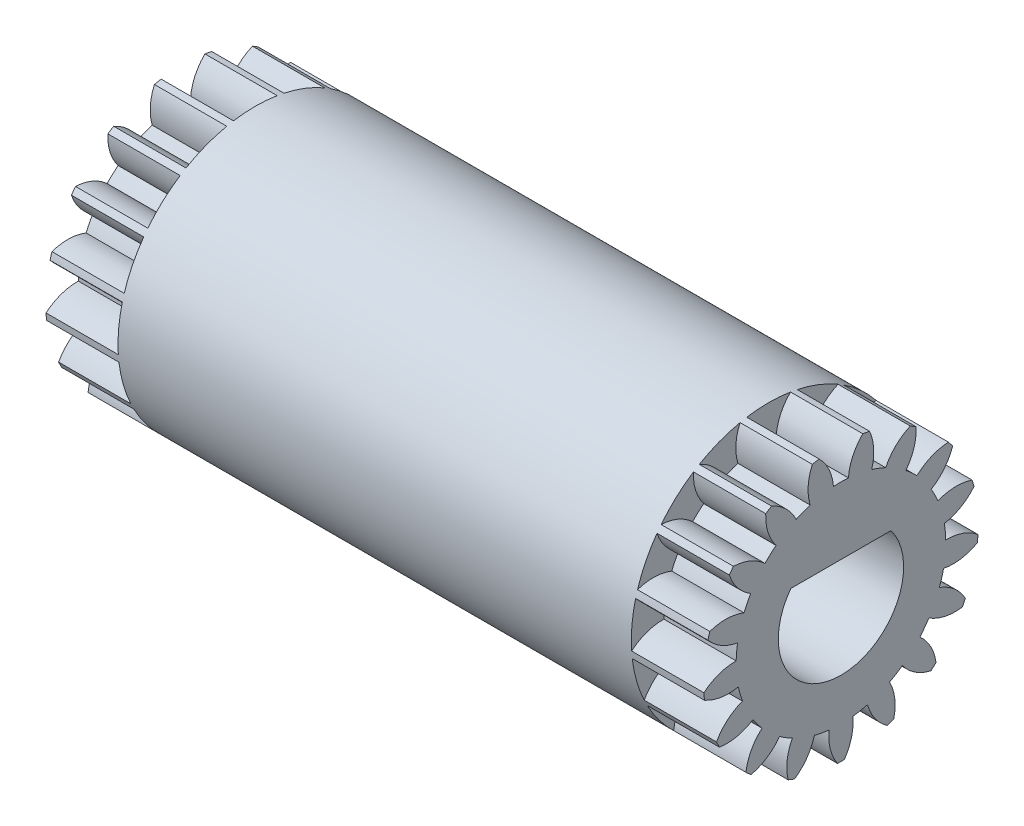
SolidWorks part; units mm, degrees
ref_plane "Plane1" through (0, 0, 0) normal (0, 0, 1) x (1, 0, 0)
ref_plane "Plane2" through (0, 0, 0) normal (0, 1, 0) x (1, 0, 0)
ref_plane "Plane3" through (0, 0, 0) normal (1, 0, 0) x (0, 0, -1)
other "Configuration Table"
sketch "HoldingSke" plane through (0, 0, 0) normal (0, 1, 0) x (1, 0, 0)
  line L0 (0, 0) -> (1.5938, -0.4873)
  line L1 (-15, 0) -> (100, 0) construction
  line L2 (0, 0) -> (-2.1039, 2.3779)
  line L3 (0, 0) -> (-11.863, 4.5341)
  line L4 (0, 0) -> (8.2586, 2.5249)
  line L5 (0, 0) -> (-46.8476, -17.4728)
  line L6 (0, 0) -> (-2.4869, -1.6779)
  line L7 (-2.1039, 2.3779) -> (8.6586, 51.2059)
  line L8 (-76.2, 54.61) -> (-75.3, 54.61)
  line L9 (-71.009, 38.7566) -> (-53.1078, 45.2721)
  line L10 (-76.2, 71.12) -> (104.1128, 71.12)
  line L11 (0, 0) -> (-3, 0)
  line L12 (-76.2, 101.6) -> (-76.177, 101.6)
  line L13 (24.9733, 27.94) -> (52.9518, 28.4284)
  line L14 (24.9733, 27.94) -> (24.9743, 27.94)
  line L15 (24.9733, 27.94) -> (100.4006, 29.5858)
  line L16 (-63.627, -0.6) -> (-12.827, -0.6)
  circle A0 centre (0, 0) radius 2.5
  circle A1 centre (0, 0) radius 1.5
  circle A2 centre (0, 0) radius 1.5
  circle A3 centre (0, 0) radius 2.5
  dimension "Num_teeth" = 17
  dimension "Pitch_radius" = 180.3128
  dimension "Width" = 3
  dimension "Thickness" = 3
sketch "BasProSke" plane through (0, 0, 0) normal (0, 1, 0) x (1, 0, 0)
  line L0 (-10, 0) -> (60, 0) construction
  line L1 (0, 0) -> (0, 5.7)
  line L2 (0, 0) -> (3, 0)
  line L3 (3, 0) -> (3, 5.7)
  line L4 (3, 5.7) -> (0, 5.7)
  dimension "Thickness" = 3
  dimension "Diameter" = 11.4
revolve "Base-Revolve" add sketch "BasProSke" angle 360 about L0
sketch "TooCutSke" plane through (0, 0, 0) normal (1, 0, 0) x (0, 0, -1)
  line L1 (0, 0) -> (0, 107) construction
  line L2 (0, 0) -> (-0.5108, 5.0744) construction
  line L3 (0, 0) -> (-1.8676, 9.9906) construction
  line L4 (-0.5108, 5.0744) -> (-0.9338, 4.9953) construction
  arc A0 (0.3104, 4.3379) -> (-0.3104, 4.3379) centre (0, 0) ccw
  arc A1 (0.9293, 5.6495) -> (-0.9293, 5.6495) centre (0, 0) ccw
  circle A2 centre (0, 0) radius 5.1 construction
  circle A3 centre (0, 0) radius 4.7924 construction
  arc A4 (-0.3104, 4.3379) -> (-0.9293, 5.6495) centre (-2.3443, 4.1799) ccw
  arc A5 (0.9293, 5.6495) -> (0.3104, 4.3379) centre (2.3443, 4.1799) ccw
extrude "ToothCut" cut sketch "TooCutSke" along normal through all
fillet "Breaks" [suppressed] radius 0.012 tangent propagation no
fillet "RootFillets" [suppressed] radius 0.151
pattern_circular "TeethCuts" count 17 every 21.176 about axis through (-10, 0, 0) along (1, 0, 0) of "ToothCut", "RootFillets", "Breaks"
sketch "HubNeaOneSke" plane through (0, 0, 0) normal (-1, 0, 0) x (0, 0, 1)
  circle A0 centre (0, 0) radius 1.5
  dimension "Diameter" = 3
extrude "HubNearOne" [suppressed] add sketch "HubNeaOneSke" along normal blind 47.0001
sketch "HubNeaBotSke" plane through (0, 0, 0) normal (-1, 0, 0) x (0, 0, 1)
  circle A0 centre (0, 0) radius 1.5
  dimension "Diameter" = 3
extrude "HubNearBoth" add sketch "HubNeaBotSke" along normal blind 23.5
ref_plane "FarPln" through (3, 0, 0) normal (1, 0, 0) x (0, 0, -1)
sketch "HubFarSke" plane through (3, 0, 0) normal (1, 0, 0) x (0, 0, -1)
  circle A0 centre (0, 0) radius 1.5
  dimension "Diameter" = 3
extrude "HubFar" add sketch "HubFarSke" along normal blind 23.5
sketch "BorSke" plane through (0, 0, 0) normal (1, 0, 0) x (0, 0, -1)
  circle A0 centre (0, 0) radius 2.5
  dimension "Diameter" = 5
extrude "Bore" cut sketch "BorSke" along normal mid plane 100.0001
sketch "KeySke" plane through (0, 0, 0) normal (1, 0, 0) x (0, 0, -1)
  line L0 (-1, 0) -> (-1, 3.4)
  line L1 (-1, 3.4) -> (1, 3.4)
  line L2 (1, 3.4) -> (1, 0)
  line L3 (0, 0) -> (0, 34) construction
  line L4 (-1, 0) -> (1, 0)
  dimension "Width" = 2
extrude "Keyway" [suppressed] cut sketch "KeySke" along normal mid plane 100.0001
pattern_circular "Keyway2" [suppressed] count 2 every 90 about axis through (-10, 0, 0) along (1, 0, 0) reverse direction yes
sketch "草图2" plane through (3, 0, 0) normal (1, 0, 0) x (0, 0, -1)
  circle A0 centre (0, 0) radius 5.7
extrude "凸台-拉伸1" add sketch "草图2" along normal blind 21.3
sketch "草图3" plane through (24.3, 0, 0) normal (1, 0, 0) x (0, 0, -1)
  arc A68 (-5.5197, 1.4221) -> (-4.2908, 0.7093) centre (-3.9458, 2.7199) ccw
  arc A69 (-5.4416, 1.6967) -> (-5.5197, 1.4221) centre (0, 0) ccw
  arc A70 (-4.0215, 1.6557) -> (-5.4416, 1.6967) centre (-4.7867, -0.2353) ccw
  arc A71 (-3.7448, 2.2114) -> (-4.0215, 1.6557) centre (0, 0) ccw
  arc A72 (-4.6333, 3.3201) -> (-3.7448, 2.2114) centre (-2.6968, 3.9617) ccw
  arc A73 (-4.4613, 3.5478) -> (-4.6333, 3.3201) centre (0, 0) ccw
  arc A74 (-3.1518, 2.9966) -> (-4.4613, 3.5478) centre (-4.5484, 1.5097) ccw
  arc A75 (-2.6931, 3.4149) -> (-3.1518, 2.9966) centre (0, 0) ccw
  arc A76 (-3.1211, 4.7696) -> (-2.6931, 3.4149) centre (-1.0836, 4.6683) ccw
  arc A77 (-2.8784, 4.9198) -> (-3.1211, 4.7696) centre (0, 0) ccw
  arc A78 (-1.8565, 3.9329) -> (-2.8784, 4.9198) centre (-3.6959, 3.0508) ccw
  arc A79 (-1.2776, 4.1571) -> (-1.8565, 3.9329) centre (0, 0) ccw
  arc A80 (-1.1873, 5.575) -> (-1.2776, 4.1571) centre (0.676, 4.7445) ccw
  arc A81 (-0.9068, 5.6274) -> (-1.1873, 5.575) centre (0, 0) ccw
  arc A82 (-0.3104, 4.3379) -> (-0.9068, 5.6274) centre (-2.3443, 4.1799) ccw
  arc A83 (0.3104, 4.3379) -> (-0.3104, 4.3379) centre (0, 0) ccw
  arc A84 (0.9068, 5.6274) -> (0.3104, 4.3379) centre (2.3443, 4.1799) ccw
  arc A85 (1.1873, 5.575) -> (0.9068, 5.6274) centre (0, 0) ccw
  arc A86 (1.2776, 4.1571) -> (1.1873, 5.575) centre (-0.676, 4.7445) ccw
  arc A87 (1.8565, 3.9329) -> (1.2776, 4.1571) centre (0, 0) ccw
  arc A88 (2.8784, 4.9198) -> (1.8565, 3.9329) centre (3.6959, 3.0508) ccw
  arc A89 (3.1211, 4.7696) -> (2.8784, 4.9198) centre (0, 0) ccw
  arc A90 (2.6931, 3.4149) -> (3.1211, 4.7696) centre (1.0836, 4.6683) ccw
  arc A91 (3.1518, 2.9966) -> (2.6931, 3.4149) centre (0, 0) ccw
  arc A92 (4.4613, 3.5478) -> (3.1518, 2.9966) centre (4.5484, 1.5097) ccw
  arc A93 (4.6333, 3.3201) -> (4.4613, 3.5478) centre (0, 0) ccw
  arc A94 (3.7448, 2.2114) -> (4.6333, 3.3201) centre (2.6968, 3.9617) ccw
  arc A95 (4.0215, 1.6557) -> (3.7448, 2.2114) centre (0, 0) ccw
  arc A96 (5.4416, 1.6967) -> (4.0215, 1.6557) centre (4.7867, -0.2353) ccw
  arc A97 (5.5197, 1.4221) -> (5.4416, 1.6967) centre (0, 0) ccw
  arc A98 (4.2908, 0.7093) -> (5.5197, 1.4221) centre (3.9458, 2.7199) ccw
  arc A99 (4.348, 0.0912) -> (4.2908, 0.7093) centre (0, 0) ccw
  arc A100 (5.6871, -0.3837) -> (4.348, 0.0912) centre (4.3784, -1.9486) ccw
  arc A101 (5.6607, -0.6679) -> (5.6871, -0.3837) centre (0, 0) ccw
  arc A102 (4.2573, -0.8886) -> (5.6607, -0.6679) centre (4.6619, 1.1109) ccw
  arc A103 (4.0874, -1.4857) -> (4.2573, -0.8886) centre (0, 0) ccw
  arc A104 (5.1644, -2.4122) -> (4.0874, -1.4857) centre (3.3788, -3.3987) ccw
  arc A105 (5.0372, -2.6677) -> (5.1644, -2.4122) centre (0, 0) ccw
  arc A106 (3.6488, -2.3665) -> (5.0372, -2.6677) centre (4.7484, -0.6482) ccw
  arc A107 (3.2747, -2.8619) -> (3.6488, -2.3665) centre (0, 0) ccw
  arc A108 (3.9443, -4.1149) -> (3.2747, -2.8619) centre (1.9229, -4.3897) ccw
  arc A109 (3.7334, -4.3072) -> (3.9443, -4.1149) centre (0, 0) ccw
  arc A110 (2.5475, -3.5248) -> (3.7334, -4.3072) centre (4.1936, -2.3198) ccw
  arc A111 (2.0197, -3.8516) -> (2.5475, -3.5248) centre (0, 0) ccw
  arc A112 (2.1915, -5.2619) -> (2.0197, -3.8516) centre (0.2073, -4.7879) ccw
  arc A113 (1.9254, -5.365) -> (2.1915, -5.2619) centre (0, 0) ccw
  arc A114 (1.1022, -4.207) -> (1.9254, -5.365) centre (3.0724, -3.678) ccw
  arc A115 (0.492, -4.3211) -> (1.1022, -4.207) centre (0, 0) ccw
  arc A116 (0.1427, -5.6982) -> (0.492, -4.3211) centre (-1.5363, -4.5395) ccw
  arc A117 (-0.1427, -5.6982) -> (0.1427, -5.6982) centre (0, 0) ccw
  arc A118 (-0.492, -4.3211) -> (-0.1427, -5.6982) centre (1.5363, -4.5395) ccw
  arc A119 (-1.1022, -4.207) -> (-0.492, -4.3211) centre (0, 0) ccw
  arc A120 (-1.9254, -5.365) -> (-1.1022, -4.207) centre (-3.0724, -3.678) ccw
  arc A121 (-2.1915, -5.2619) -> (-1.9254, -5.365) centre (0, 0) ccw
  arc A122 (-2.0197, -3.8516) -> (-2.1915, -5.2619) centre (-0.2073, -4.7879) ccw
  arc A123 (-2.5475, -3.5248) -> (-2.0197, -3.8516) centre (0, 0) ccw
  arc A124 (-3.7334, -4.3072) -> (-2.5475, -3.5248) centre (-4.1936, -2.3198) ccw
  arc A125 (-3.9443, -4.1149) -> (-3.7334, -4.3072) centre (0, 0) ccw
  arc A126 (-3.2747, -2.8619) -> (-3.9443, -4.1149) centre (-1.9229, -4.3897) ccw
  arc A127 (-3.6488, -2.3665) -> (-3.2747, -2.8619) centre (0, 0) ccw
  arc A128 (-5.0372, -2.6677) -> (-3.6488, -2.3665) centre (-4.7484, -0.6482) ccw
  arc A129 (-5.1644, -2.4122) -> (-5.0372, -2.6677) centre (0, 0) ccw
  arc A130 (-4.0874, -1.4857) -> (-5.1644, -2.4122) centre (-3.3788, -3.3987) ccw
  arc A131 (-4.2573, -0.8886) -> (-4.0874, -1.4857) centre (0, 0) ccw
  arc A132 (-5.6607, -0.6679) -> (-4.2573, -0.8886) centre (-4.6619, 1.1109) ccw
  arc A133 (-5.6871, -0.3837) -> (-5.6607, -0.6679) centre (0, 0) ccw
  arc A134 (-4.348, 0.0912) -> (-5.6871, -0.3837) centre (-4.3784, -1.9486) ccw
  arc A135 (-4.2908, 0.7093) -> (-4.348, 0.0912) centre (0, 0) ccw
  arc A136 (-5.5197, 1.4221) -> (-4.2908, 0.7093) centre (-3.9458, 2.7199) ccw
  arc A137 (-5.4416, 1.6967) -> (-5.5197, 1.4221) centre (0, 0) ccw
  arc A138 (-4.0215, 1.6557) -> (-5.4416, 1.6967) centre (-4.7867, -0.2353) ccw
  arc A139 (-3.7448, 2.2114) -> (-4.0215, 1.6557) centre (0, 0) ccw
  arc A140 (-4.6333, 3.3201) -> (-3.7448, 2.2114) centre (-2.6968, 3.9617) ccw
  arc A141 (-4.4613, 3.5478) -> (-4.6333, 3.3201) centre (0, 0) ccw
  arc A142 (-3.1518, 2.9966) -> (-4.4613, 3.5478) centre (-4.5484, 1.5097) ccw
  arc A143 (-2.6931, 3.4149) -> (-3.1518, 2.9966) centre (0, 0) ccw
  arc A144 (-3.1211, 4.7696) -> (-2.6931, 3.4149) centre (-1.0836, 4.6683) ccw
  arc A145 (-2.8784, 4.9198) -> (-3.1211, 4.7696) centre (0, 0) ccw
  arc A146 (-1.8565, 3.9329) -> (-2.8784, 4.9198) centre (-3.6959, 3.0508) ccw
  arc A147 (-1.2776, 4.1571) -> (-1.8565, 3.9329) centre (0, 0) ccw
  arc A148 (-1.1873, 5.575) -> (-1.2776, 4.1571) centre (0.676, 4.7445) ccw
  arc A149 (-0.9068, 5.6274) -> (-1.1873, 5.575) centre (0, 0) ccw
  arc A150 (-0.3104, 4.3379) -> (-0.9068, 5.6274) centre (-2.3443, 4.1799) ccw
  arc A151 (0.3104, 4.3379) -> (-0.3104, 4.3379) centre (0, 0) ccw
  arc A152 (0.9068, 5.6274) -> (0.3104, 4.3379) centre (2.3443, 4.1799) ccw
  arc A153 (1.1873, 5.575) -> (0.9068, 5.6274) centre (0, 0) ccw
  arc A154 (1.2776, 4.1571) -> (1.1873, 5.575) centre (-0.676, 4.7445) ccw
  arc A155 (1.8565, 3.9329) -> (1.2776, 4.1571) centre (0, 0) ccw
  arc A156 (2.8784, 4.9198) -> (1.8565, 3.9329) centre (3.6959, 3.0508) ccw
  arc A157 (3.1211, 4.7696) -> (2.8784, 4.9198) centre (0, 0) ccw
  arc A158 (2.6931, 3.4149) -> (3.1211, 4.7696) centre (1.0836, 4.6683) ccw
  arc A159 (3.1518, 2.9966) -> (2.6931, 3.4149) centre (0, 0) ccw
  arc A160 (4.4613, 3.5478) -> (3.1518, 2.9966) centre (4.5484, 1.5097) ccw
  arc A161 (4.6333, 3.3201) -> (4.4613, 3.5478) centre (0, 0) ccw
  arc A162 (3.7448, 2.2114) -> (4.6333, 3.3201) centre (2.6968, 3.9617) ccw
  arc A163 (4.0215, 1.6557) -> (3.7448, 2.2114) centre (0, 0) ccw
  arc A164 (5.4416, 1.6967) -> (4.0215, 1.6557) centre (4.7867, -0.2353) ccw
  arc A165 (5.5197, 1.4221) -> (5.4416, 1.6967) centre (0, 0) ccw
  arc A166 (4.2908, 0.7093) -> (5.5197, 1.4221) centre (3.9458, 2.7199) ccw
  arc A167 (4.348, 0.0912) -> (4.2908, 0.7093) centre (0, 0) ccw
  arc A168 (5.6871, -0.3837) -> (4.348, 0.0912) centre (4.3784, -1.9486) ccw
  arc A169 (5.6607, -0.6679) -> (5.6871, -0.3837) centre (0, 0) ccw
  arc A170 (4.2573, -0.8886) -> (5.6607, -0.6679) centre (4.6619, 1.1109) ccw
  arc A171 (4.0874, -1.4857) -> (4.2573, -0.8886) centre (0, 0) ccw
  arc A172 (5.1644, -2.4122) -> (4.0874, -1.4857) centre (3.3788, -3.3987) ccw
  arc A173 (5.0372, -2.6677) -> (5.1644, -2.4122) centre (0, 0) ccw
  arc A174 (3.6488, -2.3665) -> (5.0372, -2.6677) centre (4.7484, -0.6482) ccw
  arc A175 (3.2747, -2.8619) -> (3.6488, -2.3665) centre (0, 0) ccw
  arc A176 (3.9443, -4.1149) -> (3.2747, -2.8619) centre (1.9229, -4.3897) ccw
  arc A177 (3.7334, -4.3072) -> (3.9443, -4.1149) centre (0, 0) ccw
  arc A178 (2.5475, -3.5248) -> (3.7334, -4.3072) centre (4.1936, -2.3198) ccw
  arc A179 (2.0197, -3.8516) -> (2.5475, -3.5248) centre (0, 0) ccw
  arc A180 (2.1915, -5.2619) -> (2.0197, -3.8516) centre (0.2073, -4.7879) ccw
  arc A181 (1.9254, -5.365) -> (2.1915, -5.2619) centre (0, 0) ccw
  arc A182 (1.1022, -4.207) -> (1.9254, -5.365) centre (3.0724, -3.678) ccw
  arc A183 (0.492, -4.3211) -> (1.1022, -4.207) centre (0, 0) ccw
  arc A184 (0.1427, -5.6982) -> (0.492, -4.3211) centre (-1.5363, -4.5395) ccw
  arc A185 (-0.1427, -5.6982) -> (0.1427, -5.6982) centre (0, 0) ccw
  arc A186 (-0.492, -4.3211) -> (-0.1427, -5.6982) centre (1.5363, -4.5395) ccw
  arc A187 (-1.1022, -4.207) -> (-0.492, -4.3211) centre (0, 0) ccw
  arc A188 (-1.9254, -5.365) -> (-1.1022, -4.207) centre (-3.0724, -3.678) ccw
  arc A189 (-2.1915, -5.2619) -> (-1.9254, -5.365) centre (0, 0) ccw
  arc A190 (-2.0197, -3.8516) -> (-2.1915, -5.2619) centre (-0.2073, -4.7879) ccw
  arc A191 (-2.5475, -3.5248) -> (-2.0197, -3.8516) centre (0, 0) ccw
  arc A192 (-3.7334, -4.3072) -> (-2.5475, -3.5248) centre (-4.1936, -2.3198) ccw
  arc A193 (-3.9443, -4.1149) -> (-3.7334, -4.3072) centre (0, 0) ccw
  arc A194 (-3.2747, -2.8619) -> (-3.9443, -4.1149) centre (-1.9229, -4.3897) ccw
  arc A195 (-3.6488, -2.3665) -> (-3.2747, -2.8619) centre (0, 0) ccw
  arc A196 (-5.0372, -2.6677) -> (-3.6488, -2.3665) centre (-4.7484, -0.6482) ccw
  arc A197 (-5.1644, -2.4122) -> (-5.0372, -2.6677) centre (0, 0) ccw
  arc A198 (-4.0874, -1.4857) -> (-5.1644, -2.4122) centre (-3.3788, -3.3987) ccw
  arc A199 (-4.2573, -0.8886) -> (-4.0874, -1.4857) centre (0, 0) ccw
  arc A200 (-5.6607, -0.6679) -> (-4.2573, -0.8886) centre (-4.6619, 1.1109) ccw
  arc A201 (-5.6871, -0.3837) -> (-5.6607, -0.6679) centre (0, 0) ccw
  arc A202 (-4.348, 0.0912) -> (-5.6871, -0.3837) centre (-4.3784, -1.9486) ccw
  arc A203 (-4.2908, 0.7093) -> (-4.348, 0.0912) centre (0, 0) ccw
  dimension "D1" = 0
extrude "凸台-拉伸2" add sketch "草图3" along normal blind 3
sketch "草图4" plane through (27.3, 0, 0) normal (1, 0, 0) x (0, 0, -1)
  circle A0 centre (0, 0) radius 2.6
extrude "切除-拉伸1" cut sketch "草图4" against normal through all
sketch "草图5" plane through (27.3, 0, 0) normal (1, 0, 0) x (0, 0, -1)
  line L0 (-2.08, 1.56) -> (2.08, 1.56)
  arc A0 (2.08, 1.56) -> (-2.08, 1.56) centre (0, 0) ccw
  dimension "D1" = 1.56
extrude "凸台-拉伸3" add sketch "草图5" against normal up to surface (27.3 mm away) up to face at (0, 0, -2.6)
equation "' \"Module@HoldingSke\" = 6.35"
equation "' \"Num_teeth@HoldingSke\" = 12"
equation "' \"Ap@HoldingSke\" =  20"
equation "' \"Ap@HoldingSke\" = 20"
equation "' \"Width@HoldingSke\" = 0.5 * 25.4"
equation "' \"Hub_dia@HoldingSke\"= 1 * 25.4"
equation "' \"Hub_dia@HoldingSke\" = 1 * 25.4"
equation "' \"Overall_len@HoldingSke\" = 1.0 * 25.4"
equation "' \"Bore@HoldingSke\" = 0.75 * 25.4"
equation "' \"T_dim@HoldingSke\" = 0.1 * 25.4"
equation "' \"Width@KeySke\" = 0.25 * 25.4"
equation "' \"Show_teeth@HoldingSke\" = 13"
equation "' \"Backlash@HoldingSke\" = 0.009 * 25.4"
equation "' \"Addendum_fac@HoldingSke\" = 1.0"
equation "' \"Dedendum_fac@HoldingSke\" = 1.25"
equation "' \"Dedendum_add@HoldingSke\" = 0.00005 * 25.4"
equation "' \"Clearance_fac@HoldingSke\" = 0.25"
equation "\"Pitch@HoldingSke\" = 1 / \"Module@HoldingSke\""
equation "\"Overcut_dia@TooCutSke\" = (\"Num_teeth@HoldingSke\" + 2 * \"Addendum_fac@HoldingSke\") / \"Pitch@HoldingSke\" + 0.002 * 25.4"
equation "\"Pitch_dia@TooCutSke\" = \"Num_teeth@HoldingSke\" / \"Pitch@HoldingSke\""
equation "\"Base_dia@TooCutSke\" = \"Num_teeth@HoldingSke\" / \"Pitch@HoldingSke\" * cos((\"Ap@HoldingSke\"  * 3.14159265 / 180))"
equation "\"Root_dia@TooCutSke\" = (\"Num_teeth@HoldingSke\" + 2) / \"Pitch@HoldingSke\" - 2 * (\"Addendum_fac@HoldingSke\" + \"Dedendum_fac@HoldingSke\") / \"Pitch@HoldingSke\" - \"Dedendum_add@HoldingSke\" * 2"
equation "\"Half_ang@TooCutSke\" = 180 / \"Num_teeth@HoldingSke\""
equation "\"Half_CT@TooCutSke\" = \"Num_teeth@HoldingSke\" / \"Pitch@HoldingSke\" * sin((3.14159265 / 2 / \"Num_teeth@HoldingSke\")) / 2 - 7 * \"Backlash@HoldingSke\" / 4"
equation "\"Flank_rad@TooCutSke\" = \"Num_teeth@HoldingSke\" / \"Pitch@HoldingSke\" / 5"
equation "\"Radius@RootFillets\" = \"Clearance_fac@HoldingSke\" / \"Pitch@HoldingSke\" + \"Dedendum_add@HoldingSke\""
equation "\"Break_rad@Breaks\" = 0.02 / \"Pitch@HoldingSke\""
equation "\"Thickness@HoldingSke\" = \"Width@HoldingSke\""
equation "\"OAL@HoldingSke\" = \"Thickness@HoldingSke\""
equation "\"MHD@HoldingSke\" = (\"Num_teeth@HoldingSke\" + 2) / \"Pitch@HoldingSke\" - 2 * (\"Addendum_fac@HoldingSke\" + \"Dedendum_fac@HoldingSke\")  / \"Pitch@HoldingSke\" - \"Dedendum_add@HoldingSke\" * 2"
equation "\"MBD@HoldingSke\" = (\"Num_teeth@HoldingSke\" + 2) / \"Pitch@HoldingSke\" - 2 * (\"Addendum_fac@HoldingSke\" + \"Dedendum_fac@HoldingSke\")  / \"Pitch@HoldingSke\" - \"Dedendum_add@HoldingSke\" * 2 - 0.002 * 25.4"
equation "\"MHD@HoldingSke\" = ((sgn( \"MHD@HoldingSke\" - \"Hub_dia@HoldingSke\" )-1)*( \"MHD@HoldingSke\" - \"Hub_dia@HoldingSke\" ))/-2+ \"Hub_dia@HoldingSke\""
equation "\"MBD@HoldingSke\" = ((sgn( \"MBD@HoldingSke\" - \"Bore@HoldingSke\" )-1)*( \"MBD@HoldingSke\" - \"Bore@HoldingSke\" ))/-2+ \"Bore@HoldingSke\""
equation "\"OAL@HoldingSke\" = ((sgn( \"OAL@HoldingSke\" - \"Overall_len@HoldingSke\" )+1)*( \"OAL@HoldingSke\" - \"Overall_len@HoldingSke\" ))/2 + \"Overall_len@HoldingSke\" + 0.000002 * 25.4"
equation "\"Num_teeth@TeethCuts\" = int( \"Show_teeth@HoldingSke\" ) + 1"
equation "\"Num_teeth@TeethCuts\" = ((sgn( \"Num_teeth@TeethCuts\" - \"Num_teeth@HoldingSke\" )-1)*( \"Num_teeth@TeethCuts\" - \"Num_teeth@HoldingSke\" ))/-2+ \"Num_teeth@HoldingSke\""
equation "\"Num_teeth@TeethCuts\" = ((sgn( \"Num_teeth@TeethCuts\" - 2.0)+1)*( \"Num_teeth@TeethCuts\" - 2.0))/2 +2.0"
equation "\"Angle@TeethCuts\" = 360.0 / \"Num_teeth@HoldingSke\""
equation "\"Diameter@BasProSke\" = (\"Num_teeth@HoldingSke\" + 2 * \"Addendum_fac@HoldingSke\") / \"Pitch@HoldingSke\""
equation "\"Thickness@BasProSke\"  = \"Thickness@HoldingSke\""
equation "' \"Fillet_rad@BasProSke\" =  \"Thickness@HoldingSke\" * 0.05"
equation "' \"Fillet_rad@BasProSke\" = \"Thickness@HoldingSke\" * 0.05"
equation "\"MHD@HoldingSke\" = ((sgn( \"MHD@HoldingSke\" - \"Root_dia@TooCutSke\" )-1)*( \"MHD@HoldingSke\" - \"Root_dia@TooCutSke\" ))/-2+ \"Root_dia@TooCutSke\""
equation "\"Diameter@HubNeaOneSke\" = \"MHD@HoldingSke\""
equation "\"Length@HubNearOne\" = \"OAL@HoldingSke\" - \"Thickness@BasProSke\""
equation "\"Diameter@HubNeaBotSke\" = \"MHD@HoldingSke\""
equation "\"Length@HubNearBoth\" = ( \"OAL@HoldingSke\" - \"Thickness@BasProSke\" ) / 2.0"
equation "\"Thickness@FarPln\" = \"Thickness@BasProSke\""
equation "\"Diameter@HubFarSke\" = \"MHD@HoldingSke\""
equation "\"Length@HubFar\" = ( \"OAL@HoldingSke\" - \"Thickness@BasProSke\" ) / 2.0"
equation "\"Diameter@BorSke\" = \"MBD@HoldingSke\""
equation "\"D1@Bore\" = \"OAL@HoldingSke\" * 2.0"
equation "\"D1@Keyway\" = \"OAL@HoldingSke\" * 2.0"
equation "\"Offset@KeySke\" = \"T_dim@HoldingSke\" + \"MBD@HoldingSke\" / 2.0"
